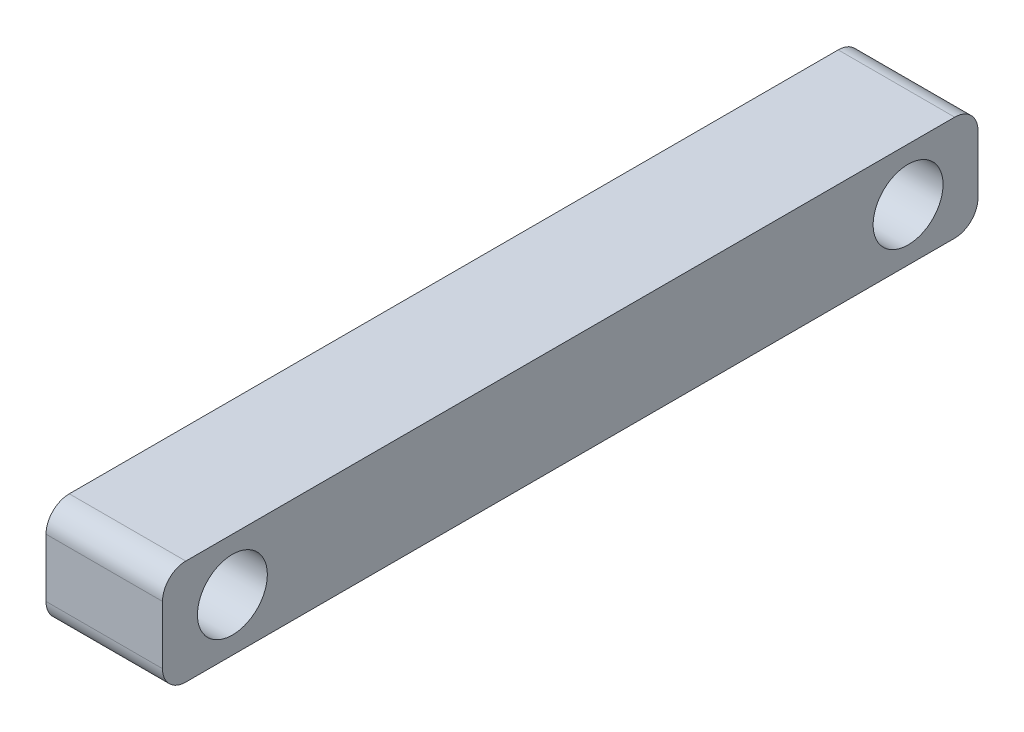
SolidWorks part; units mm, degrees
ref_plane "Alzado" through (0, 0, 0) normal (0, 0, 1) x (1, 0, 0)
ref_plane "Planta" through (0, 0, 0) normal (0, 1, 0) x (1, 0, 0)
ref_plane "Vista lateral" through (0, 0, 0) normal (1, 0, 0) x (0, 0, -1)
sketch "Croquis1" plane through (0, 0, 0) normal (1, 0, 0) x (0, 0, -1)
  line L0 (-16.5, 2.25) -> (16.5, 2.25)
  line L2 (-17.5, 0) -> (17.5, 0) construction
  line L3 (-17.5, 1.25) -> (-17.5, -1.25)
  line L4 (-16.5, -2.25) -> (16.5, -2.25)
  line L5 (17.5, 1.25) -> (17.5, -1.25)
  arc A0 (-17.5, -1.25) -> (-16.5, -2.25) centre (-16.5, -1.25) ccw
  arc A1 (-17.5, 1.25) -> (-16.5, 2.25) centre (-16.5, 1.25) cw
  arc A2 (16.5, -2.25) -> (17.5, -1.25) centre (16.5, -1.25) ccw
  arc A3 (16.5, 2.25) -> (17.5, 1.25) centre (16.5, 1.25) cw
  point P1 (0, 0)
  point P9 (-17.5, -2.25)
  point P13 (-17.5, 2.25)
  point P16 (17.5, -2.25)
  point P19 (17.5, 2.25)
  dimension "D3" = 1
  dimension "D4" = 1
  dimension "D1" = 2.25
  dimension "D2" = 35
extrude "Saliente-Extruir1" add sketch "Croquis1" along normal mid plane 5
sketch "Croquis2" plane through (0, 0, 0) normal (1, 0, 0) x (0, 0, -1)
  line L0 (-17.5, 1.25) -> (-17.5, -1.25) construction
  line L1 (17.5, -1.25) -> (17.5, 1.25) construction
  circle A0 centre (-14.5, 0) radius 1.5
  circle A1 centre (14.5, 0) radius 1.5
  dimension "D1" = 3
  dimension "D3" = 3
  dimension "D2" = 3
  dimension "D4" = 3
extrude "Cortar-Extruir1" cut sketch "Croquis2" against normal through all both and the other way through all
